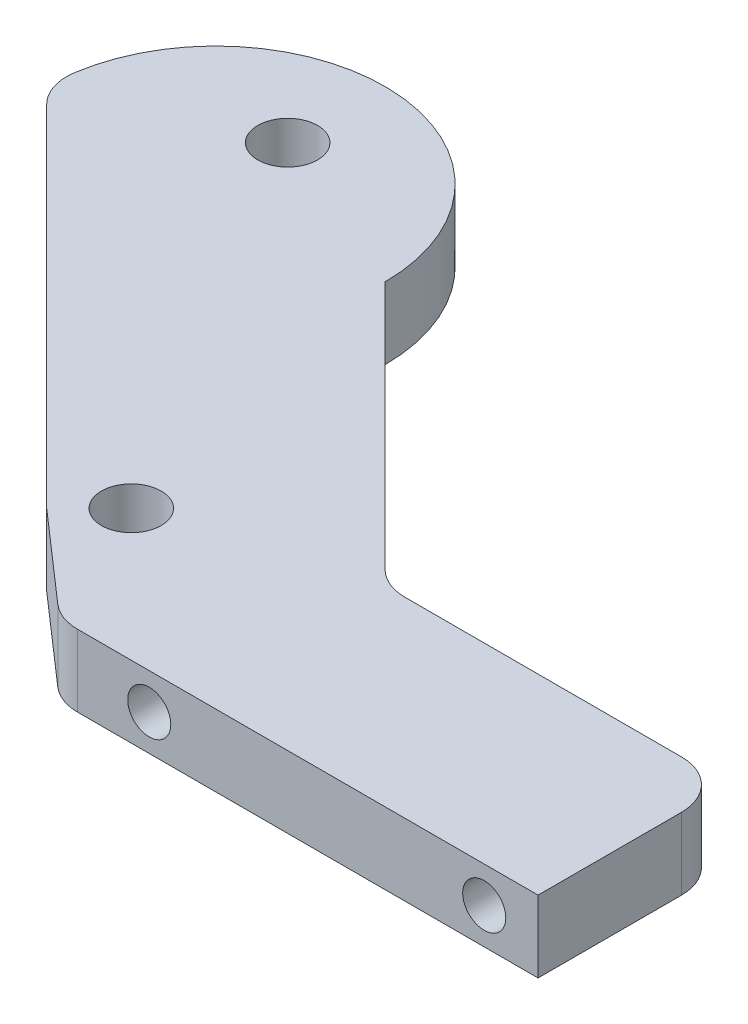
SolidWorks part; units mm, degrees
ref_plane "Front Plane" through (0, 0, 0) normal (0, 0, 1) x (1, 0, 0)
ref_plane "Top Plane" through (0, 0, 0) normal (0, 1, 0) x (1, 0, 0)
ref_plane "Right Plane" through (0, 0, 0) normal (1, 0, 0) x (0, 0, -1)
sketch "Sketch1" plane through (0, 0, 0) normal (0, 1, 0) x (1, 0, 0)
  line L0 (0, 6.35) -> (12.3665, 6.35)
  line L1 (12.3665, 6.35) -> (57.15, 6.35)
  line L2 (6.35, 0) -> (6.35, -13.97)
  line L3 (6.35, -13.97) -> (57.15, -13.97)
  line L4 (57.15, 6.35) -> (57.15, -13.97)
  line L5 (20.5908, 6.35) -> (-7.3492, 34.29)
  line L6 (-4.4901, -4.4901) -> (-43.2703, 34.29)
  line L7 (-4.4901, -4.4901) -> (6.35, -13.97)
  circle A0 centre (0, 0) radius 3.175
  arc A1 (0, 6.35) -> (6.35, 0) centre (0, 0) ccw
  arc A2 (-43.2703, 34.29) -> (-7.3492, 34.29) centre (-25.3097, 34.29) cw
  dimension "D1" = 12.7
  dimension "D2" = 6.35
  dimension "D3" = 6.35
  dimension "D4" = 50.8
  dimension "D5" = 20.32
  dimension "D6" = 45
  dimension "D7" = 25.4
  dimension "D8" = 27.94
extrude "Boss-Extrude1" add sketch "Sketch1" along normal mid plane 7.62 contours A2 L6 A1 L0 L1 L5 | L0 A1 L2 L3 L4 L1 A0 | A1 L7 L2 region at (-15.7867, 0, -26.7963) region at (28.8904, 0, 3.4247) region at (3.6646, 0, 8.0416)
sketch "Sketch2" plane through (0, 0, 13.97) normal (0, 0, 1) x (1, 0, 0)
  circle A0 centre (51.4379, 0) radius 1.8987 construction
  circle A1 centre (15.8779, 0) radius 1.8987 construction
  circle A2 centre (51.4379, 0) radius 1.8987
  circle A3 centre (15.8779, 0) radius 1.8987
  circle A4 centre (15.8779, 0) radius 2.286
  circle A5 centre (51.4379, 0) radius 2.286
  dimension "D1" = 4.572
  dimension "D2" = 4.572
extrude "Cut-Extrude1" cut sketch "Sketch2" against normal blind 5.08 contours A4 | A5 | A3 | A2 region at (51.4379, 0, 13.97) region at (15.8779, 0, 13.97) region at (13.6566, 0, 13.97) region at (49.2166, 0, 13.97)
fillet "Fillet1" radius 5.08 4 edges at (57.15, 0, -6.35) (20.5908, 0, -6.35) (6.35, 0, 13.97) (-43.2703, 0, -34.29)
sketch "Sketch3" plane through (0, 3.81, 0) normal (0, 1, 0) x (1, 0, 0)
  circle A0 centre (-25.3097, 41.91) radius 3.175
  arc A1 (-7.3492, 34.29) -> (-43.0622, 37.016) centre (-25.3097, 34.29) ccw construction
  arc A2 (-7.3492, 34.29) -> (-43.0622, 37.016) centre (-25.3097, 34.29) ccw
  dimension "D2" = 6.35
  dimension "D1" = 7.62
extrude "Cut-Extrude2" cut sketch "Sketch3" against normal through all contours A0 region at (-25.3097, 3.81, -41.91)
